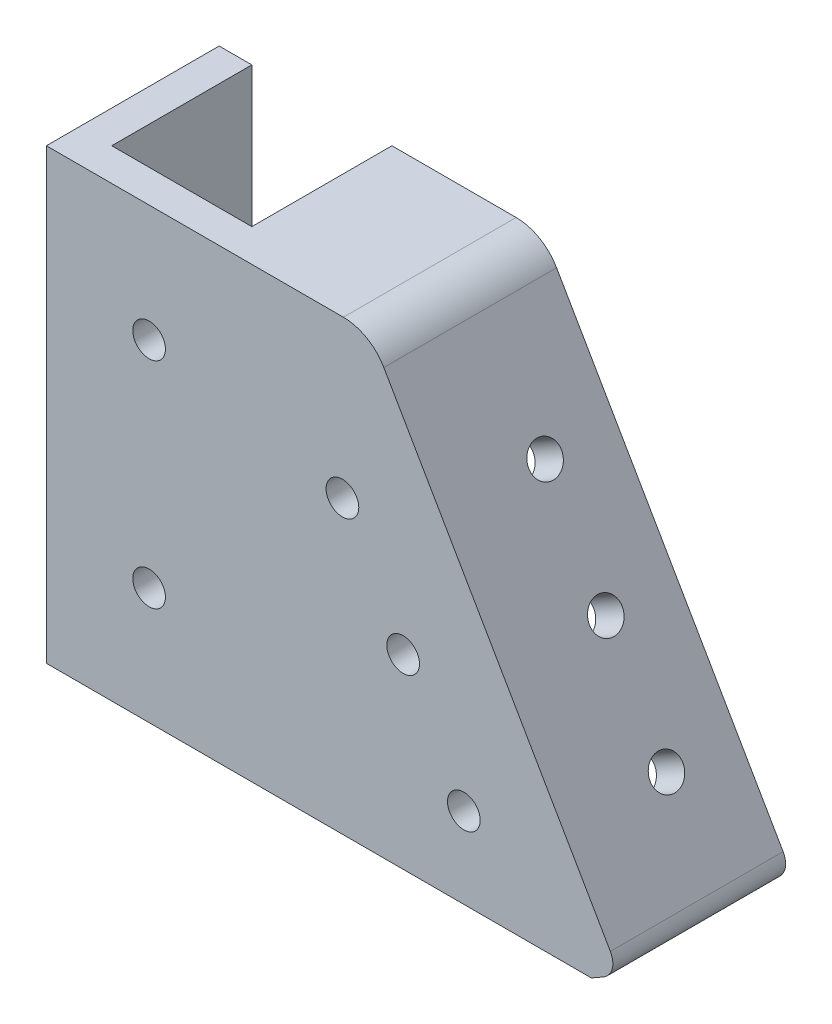
SolidWorks part; units mm, degrees
ref_plane "Front Plane" through (0, 0, 0) normal (0, 0, 1) x (1, 0, 0)
ref_plane "Top Plane" through (0, 0, 0) normal (0, 1, 0) x (1, 0, 0)
ref_plane "Right Plane" through (0, 0, 0) normal (1, 0, 0) x (0, 0, -1)
sketch "Sketch1" plane through (0, 0, 0) normal (0, 0, 1) x (1, 0, 0)
  line L0 (20.5456, 15.4888) -> (48.2584, -32.5112)
  line L2 (-14.145, 15.4888) -> (-14.145, -32.5112)
  line L3 (-14.145, -32.5112) -> (7.855, -32.5112)
  line L4 (7.855, 37.4696) -> (7.855, -32.5112) construction
  line L5 (48.2584, -32.5112) -> (7.855, -32.5112)
  line L6 (22.855, -32.5112) -> (7.855, -6.5304) construction
  line L7 (7.855, -6.5304) -> (44.3314, 14.5292) construction
  line L8 (20.5456, 15.4888) -> (-14.145, 15.4888)
  dimension "D2" = 30
  dimension "D3" = 22
  dimension "D4" = 30
  dimension "D5" = 48
extrude "Boss-Extrude1" add sketch "Sketch1" along normal blind 18.5
sketch "Sketch2" plane through (0, 0, 0) normal (0, 0, 1) x (1, 0, 0)
  line L1 (-14.145, -32.5112) -> (48.2584, -32.5112) construction
  line L2 (-10.645, 15.4888) -> (4.355, 15.4888)
  line L3 (-10.645, 15.4888) -> (-10.645, -32.5112)
  line L4 (-10.645, -32.5112) -> (4.355, -32.5112)
  line L5 (4.355, 15.4888) -> (4.355, -32.5112)
  line L6 (-14.145, 15.4888) -> (-14.145, -32.5112) construction
  line L7 (44.2169, -32.5112) -> (19.8868, 9.6298)
  line L8 (19.8868, 9.6298) -> (6.8964, 2.1298)
  line L9 (6.8964, 2.1298) -> (26.8964, -32.5112)
  line L10 (26.8964, -32.5112) -> (44.2169, -32.5112)
  line L11 (48.2584, -32.5112) -> (20.5456, 15.4888) construction
  line L12 (20.5456, 15.4888) -> (-14.145, 15.4888) construction
  dimension "D1" = 15
  dimension "D2" = 3.5
  dimension "D3" = 3.5
  dimension "D4" = 15
  dimension "D5" = 40
extrude "Cut-Extrude1" cut sketch "Sketch2" along normal offset from surface (15 mm away) 15 up to face at (10.1285, -8.5112, 0)
sketch "Sketch3" plane through (22.116, 12.7687, 0) normal (0.866, 0.5, 0) x (0, 0, -1)
  line L0 (-7.5, 30.2721) -> (-7.5, -52.2847) construction
  line L2 (-18.5, -52.2847) -> (0, -52.2847) construction
  circle A0 centre (-7.5, -38.2847) radius 1.75
  circle A1 centre (-7.5, -25.2847) radius 1.75
  circle A2 centre (-7.5, -12.2847) radius 1.75
  dimension "D1" = 3.5
  dimension "D2" = 14
  dimension "D4" = 13
  dimension "D3" = 13
extrude "Cut-Extrude2" cut sketch "Sketch3" against normal blind 3.5
sketch "Sketch4" plane through (0, 0, 18.5) normal (0, 0, -1) x (-1, 0, 0)
  line L0 (3.145, 15.4888) -> (3.145, -32.5112) construction
  line L1 (-20.5456, 15.4888) -> (14.145, 15.4888) construction
  line L2 (14.145, -32.5112) -> (10.645, -32.5112) construction
  line L3 (-13.3916, 5.8798) -> (-35.5567, -32.5112) construction
  line L4 (-6.8964, 2.1298) -> (-19.8868, 9.6298) construction
  line L6 (14.145, 15.4888) -> (14.145, -32.5112) construction
  circle A0 centre (-30.5567, -23.851) radius 1.75
  circle A1 centre (-24.0567, -12.5926) radius 1.75
  circle A2 centre (-17.5567, -1.3343) radius 1.75
  circle A4 centre (3.145, 2.9888) radius 1.75
  circle A6 centre (3.145, -20.0112) radius 1.75
  circle A7 centre (3.145, 14.4888) radius 1.75 [skipped]
  circle A8 centre (3.145, -8.5112) radius 1.75 [skipped]
  dimension "D1" = 10
  dimension "D2" = 13
  dimension "D3" = 13
  dimension "D4" = 3.5
  dimension "D5" = 4
  dimension "D6" = 12.5
  dimension "D7" = 11
  dimension "D8" = 12.5
extrude "Cut-Extrude3" cut sketch "Sketch4" along normal blind 4
sketch "Sketch5" plane through (-14.145, 0, 0) normal (-1, 0, 0) x (0, 0, 1)
  line L0 (7.5, 39.9696) -> (7.5, -32.5112) construction
  line L2 (18.5, -32.5112) -> (0, -32.5112) construction
  line L3 (18.5, 15.4888) -> (0, 15.4888) construction
  line L4 (0, 15.4888) -> (0, -32.5112) construction
  circle A0 centre (7.5, -20.0112) radius 1.75
  circle A2 centre (7.5, 2.9888) radius 1.75
  circle A4 centre (7.5, 14.4888) radius 1.75 [skipped]
  circle A5 centre (7.5, -8.5112) radius 1.75 [skipped]
  dimension "D2" = 3.5
  dimension "D3" = 12.5
  dimension "D5" = 12.5
  dimension "D1" = 7.5
  dimension "D4" = 4
extrude "Cut-Extrude4" cut sketch "Sketch5" against normal blind 4
sketch "Sketch6" plane through (0, 0, 18.5) normal (0, 0, 1) x (1, 0, 0)
  line L0 (44.2169, -32.5112) -> (47.248, -30.7612)
  line L1 (48.2584, -32.5112) -> (20.5456, 15.4888) construction
  line L2 (47.248, -30.7612) -> (48.2584, -32.5112)
  line L3 (48.2584, -32.5112) -> (44.2169, -32.5112)
extrude "Cut-Extrude5" cut sketch "Sketch6" against normal blind 19
fillet "Fillet1" radius 2 1 edges at (47.248, -30.7612, 9.25)
fillet "Fillet2" radius 5 1 edges at (20.5456, 15.4888, 9.25)
